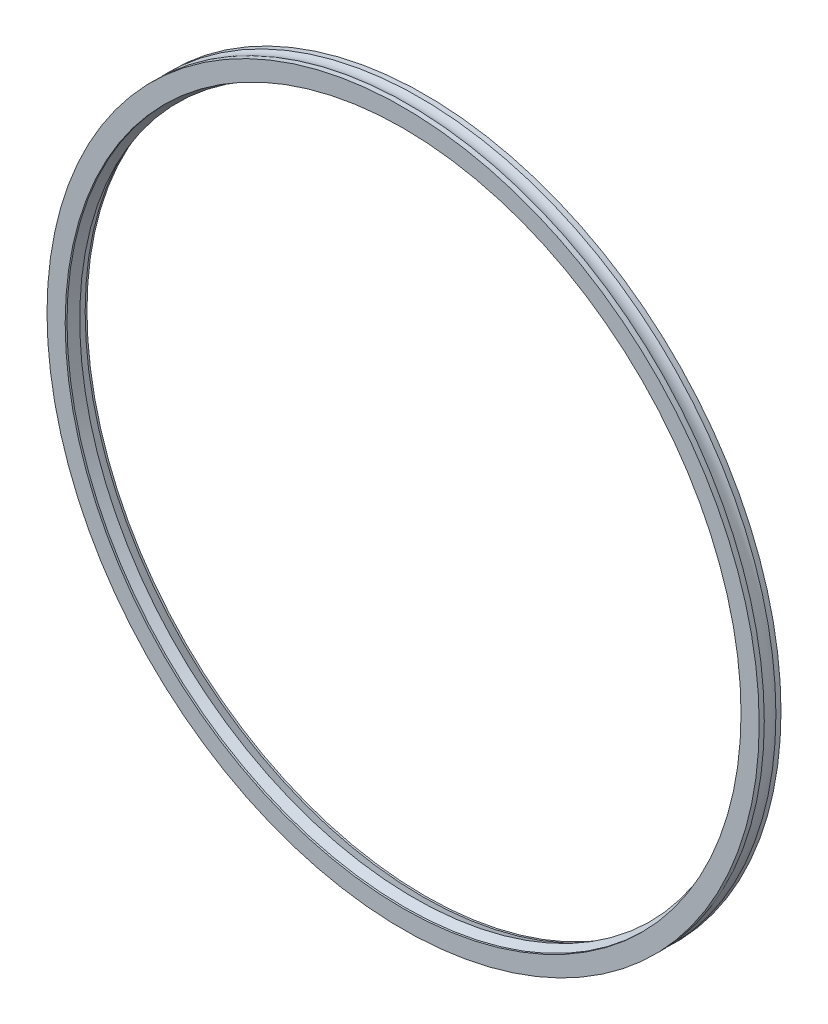
SolidWorks part; units mm, degrees
ref_plane "Front Plane" through (0, 0, 0) normal (0, 0, 1) x (1, 0, 0)
ref_plane "Top Plane" through (0, 0, 0) normal (0, 1, 0) x (1, 0, 0)
ref_plane "Right Plane" through (0, 0, 0) normal (1, 0, 0) x (0, 0, -1)
sketch "Sketch1" plane through (0, 0, 0) normal (1, 0, 0) x (0, 0, -1)
  line L0 (0, 0) -> (40.9613, 0) construction
  line L1 (0, 0) -> (0, 70.3937) construction
  line L2 (0.8, 49) -> (1.5, 49)
  line L3 (1.5, 49) -> (1.5, 46.5)
  line L6 (-1.5, 49) -> (-1.5, 46.5)
  line L7 (-0.8, 49) -> (-1.5, 49)
  line L8 (1.5, 46.5) -> (1.25, 46.5)
  line L9 (1.25, 46.5) -> (0, 46)
  line L10 (-1.25, 46.5) -> (0, 46)
  line L11 (-1.5, 46.5) -> (-1.25, 46.5)
  arc A0 (-0.8, 49) -> (0.8, 49) centre (0, 50.833) ccw
  dimension "D1" = 4
  dimension "D2" = 3
  dimension "D3" = 1.6
  dimension "D4" = 3
  dimension "D5" = 92
  dimension "D6" = 2.5
  dimension "D7" = 2.5
revolve "Revolve1" add sketch "Sketch1" angle 360 about L0
ref_axis "Axis1" through (0, 0, -1.65) along (0, 0, 1)
